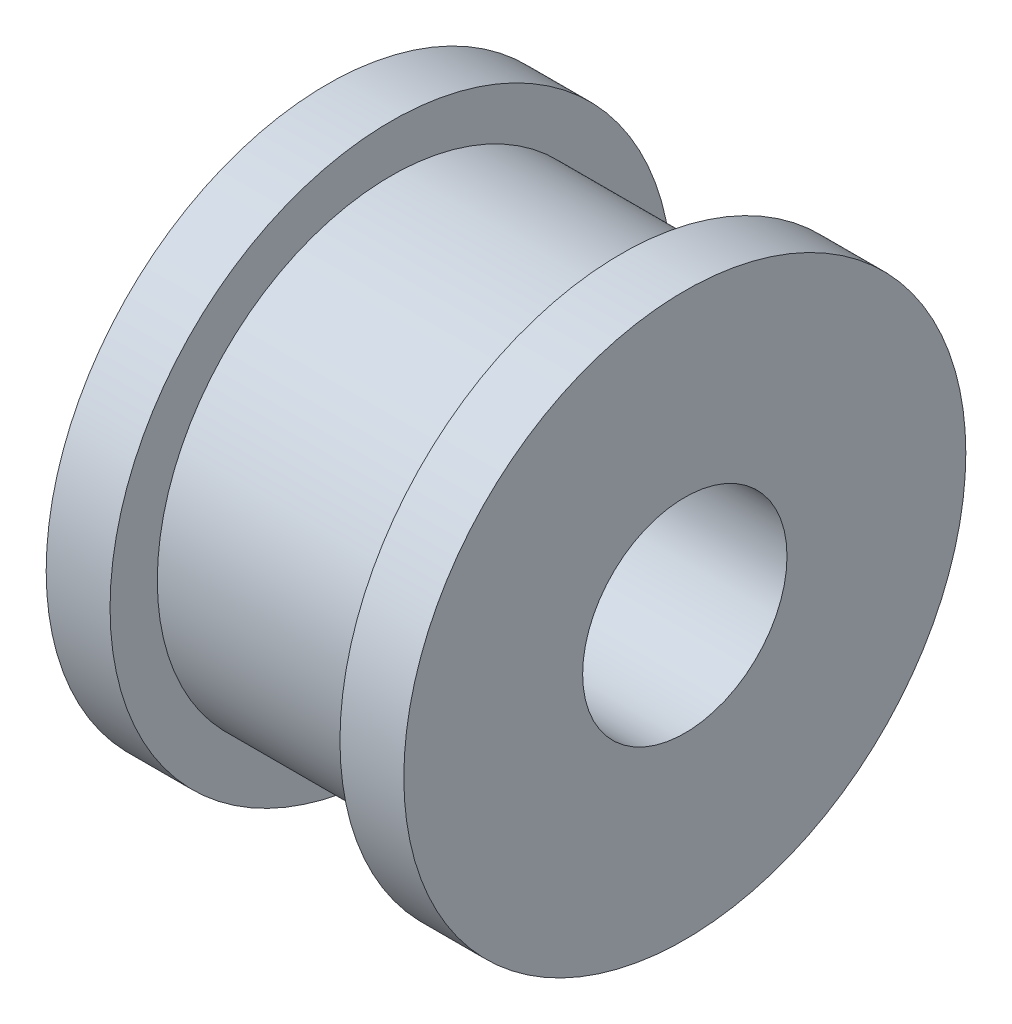
SolidWorks part; units mm, degrees
ref_plane "Front Plane" through (0, 0, 0) normal (0, 0, 1) x (1, 0, 0)
ref_plane "Top Plane" through (0, 0, 0) normal (0, 1, 0) x (1, 0, 0)
ref_plane "Right Plane" through (0, 0, 0) normal (1, 0, 0) x (0, 0, -1)
sketch "Sketch1" plane through (0, 0, 0) normal (1, 0, 0) x (0, 0, -1)
  circle A0 centre (0, 0) radius 11
  dimension "D1" = 22
extrude "Boss-Extrude1" add sketch "Sketch1" along normal blind 2.5
sketch "Sketch2" plane through (2.5, 0, 0) normal (1, 0, 0) x (0, 0, -1)
  circle A0 centre (0, 0) radius 9.15
  dimension "D1" = 18.3
extrude "Boss-Extrude2" add sketch "Sketch2" along normal blind 9
sketch "Sketch3" plane through (11.5, 0, 0) normal (1, 0, 0) x (0, 0, -1)
  circle A0 centre (0, 0) radius 11
extrude "Boss-Extrude3" add sketch "Sketch3" along normal blind 2.5
sketch "Sketch4" plane through (14, 0, 0) normal (1, 0, 0) x (0, 0, -1)
  circle A0 centre (0, 0) radius 4
  dimension "D1" = 8
extrude "Cut-Extrude1" cut sketch "Sketch4" against normal through all
